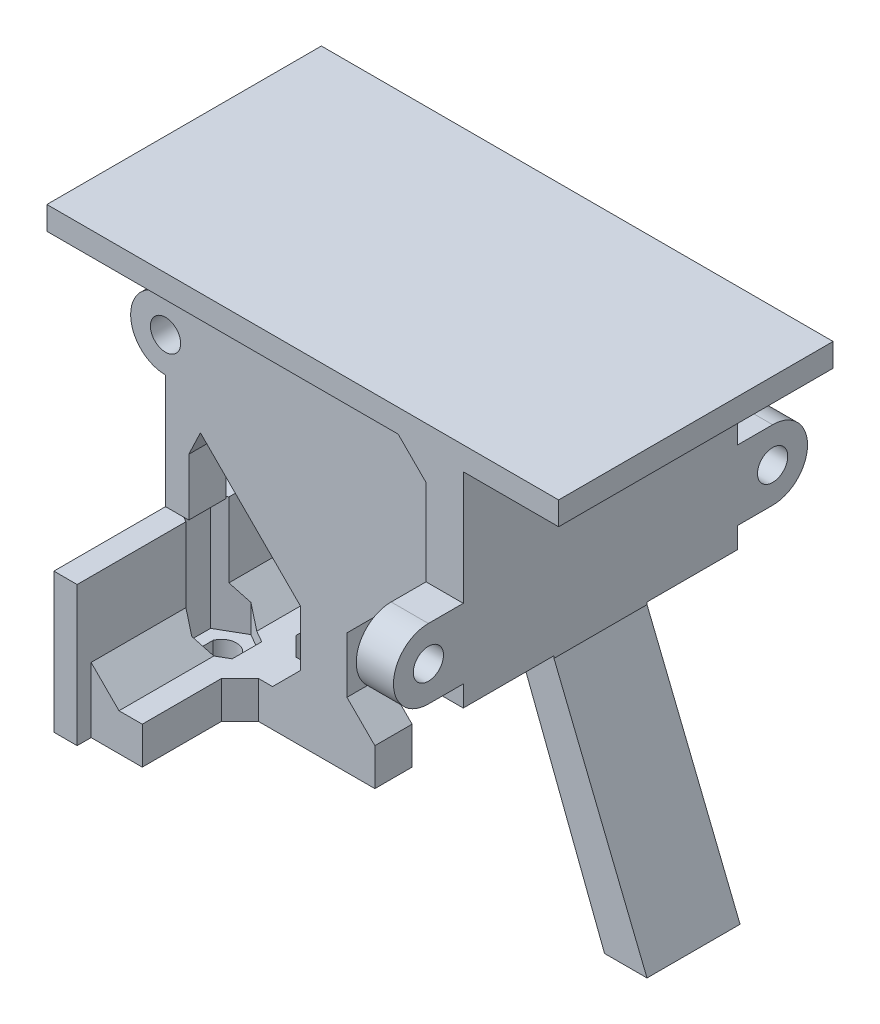
SolidWorks part; units mm, degrees
ref_plane "Alzado" through (0, 0, 0) normal (0, 0, 1) x (1, 0, 0)
ref_plane "Planta" through (0, 0, 0) normal (0, 1, 0) x (1, 0, 0)
ref_plane "Vista lateral" through (0, 0, 0) normal (1, 0, 0) x (0, 0, -1)
sketch "Croquis1" plane through (0, 0, 0) normal (0, 0, 1) x (1, 0, 0)
  line L0 (-14.75, 6) -> (-14.75, 3.75)
  line L1 (-14.75, 6) -> (14.75, 6)
  line L3 (-14.75, -6) -> (14.75, -6)
  line L5 (-14.75, 4.0227) -> (22, -6) construction
  line L6 (-22, -6) -> (22, 6) construction
  line L7 (-14.75, 3.75) -> (-18.5, 3.75)
  line L8 (-18.5, -3.75) -> (-14.75, -3.75)
  line L9 (-14.75, -3.75) -> (-14.75, -6)
  line L10 (14.75, -6) -> (14.75, -3.75)
  line L11 (14.75, -3.75) -> (18.5, -3.75)
  line L12 (14.75, 6) -> (14.75, 3.75)
  line L13 (14.75, 3.75) -> (18.5, 3.75)
  circle A0 centre (-18.5, 0) radius 1.625
  circle A1 centre (18.5, 0) radius 1.625
  arc A2 (-18.5, 3.75) -> (-18.5, -3.75) centre (-18.5, 0) ccw
  arc A3 (18.5, -3.75) -> (18.5, 3.75) centre (18.5, 0) ccw
  point P0 (0, 0)
  dimension "D1" = 3.25
  dimension "D6" = 7.5
  dimension "D7" = 7.5
  dimension "D2" = 37
  dimension "D3" = 18.5
  dimension "D5" = 12
extrude "Saliente-Extruir1" add sketch "Croquis1" along normal blind 4
sketch "Croquis2" plane through (0, 0, 4) normal (0, 0, 1) x (1, 0, 0)
  line L0 (-14.75, -6) -> (14.75, -6) construction
  line L1 (-4, -6) -> (1, -6)
  line L2 (-4, -6) -> (-4, -31)
  line L3 (-4, -31) -> (1, -31)
  line L4 (1, -6) -> (1, -31)
  dimension "D1" = 5
  dimension "D2" = 4
  dimension "D3" = 25
extrude "Saliente-Extruir2" add sketch "Croquis2" against normal blind 4
sketch "Croquis3" plane through (0, -31, 0) normal (0, -1, 0) x (1, 0, 0)
  line L0 (-10.5, -1.5) -> (-10.5, -10.5)
  line L5 (-18.5, 14.5) -> (-10.5, 14.5)
  line L6 (-18.5, 14.5) -> (-18.5, -10.5)
  line L7 (-22.25, 2) -> (-12.4182, 2) construction
  line L13 (-18.5, -10.5) -> (-10.5, -10.5)
  line L15 (-10.5, 14.5) -> (-10.5, 5.5)
  line L16 (-10.5, 5.5) -> (4, 5.5)
  line L19 (-10.5, -1.5) -> (4, -1.5)
  line L20 (4, 5.5) -> (4, -1.5)
  line L21 (-18.5, 4) -> (-18.5, 0) construction
  circle A4 centre (-14.5, 2) radius 1.625
  dimension "D3" = 25
  dimension "D9" = 7
  dimension "D5" = 3.25
  dimension "D10" = 4
  dimension "D1" = 8
  dimension "D2" = 12.5
  dimension "D8" = 3.5
  dimension "D6" = 12.5
extrude "Saliente-Extruir3" add sketch "Croquis3" against normal blind 4
chamfer "Chaflán1" distance 3 angle 45 1 edges at (-4, -27, 2)
chamfer "Chaflán2" distance 1.5 angle 45 2 edges at (-10.5, -29, -1.5) (-10.5, -29, 5.5)
sketch "Croquis4" plane through (0, 0, 4) normal (0, 0, 1) x (1, 0, 0)
  line L1 (18.5, -6) -> (26.25, -6)
  line L2 (18.5, -6) -> (18.5, 6)
  line L3 (18.5, 6) -> (26.25, 6)
  line L4 (26.25, -6) -> (26.25, 6)
  arc A0 (18.5, -3.75) -> (18.5, 3.75) centre (18.5, 0) ccw construction
  circle A1 centre (18.5, 0) radius 1.625 construction
  point P7 (22.25, 0)
  dimension "D1" = 4
  dimension "D2" = 0
extrude "Saliente-Extruir4" add sketch "Croquis4" along normal blind 21 and the other way blind 25
sketch "Croquis5" plane through (0, 6, 0) normal (0, 1, 0) x (1, 0, 0)
  line L0 (26.25, 21) -> (18.5, 21) construction
  line L1 (18.5, 0) -> (22.25, 0)
  line L2 (18.5, 0) -> (18.5, 21)
  line L3 (18.5, 21) -> (22.25, 21)
  line L4 (22.25, 0) -> (22.25, 21)
  line L6 (18.5, -4) -> (22.25, -4)
  line L7 (18.5, -4) -> (18.5, -25)
  line L8 (18.5, -25) -> (22.25, -25)
  line L9 (22.25, -4) -> (22.25, -25)
  line L10 (26.25, -25) -> (18.5, -25) construction
  line L11 (26.25, 21) -> (26.25, -25) construction
  line L12 (14.75, -4) -> (-14.75, -4) construction
  dimension "D1" = 4
  dimension "D2" = 4
extrude "Cortar-Extruir1" cut sketch "Croquis5" against normal through all both and the other way through all
sketch "Croquis6" plane through (0, 0, 4) normal (0, 0, 1) x (1, 0, 0)
  line L0 (18.5, -1.625) -> (18.5, 1.625) construction
  line L1 (18.5, 3.75) -> (22.25, 6)
  line L2 (22.25, 6) -> (18.5, 6)
  line L3 (18.5, 6) -> (18.5, 3.75)
  line L4 (18.5, -3.75) -> (22.25, -6)
  line L5 (22.25, -6) -> (18.5, -6)
  line L6 (18.5, -6) -> (18.5, -3.75)
  circle A0 centre (18.5, 0) radius 1.625
extrude "Cortar-Extruir2" cut sketch "Croquis6" against normal through all both and the other way through all
chamfer "Chaflán4" distance 5 angle 45 2 edges at (22.25, 0, 0) (22.25, 0, 4)
sketch "Croquis7" plane through (0, 0, 4) normal (0, 0, 1) x (1, 0, 0)
  circle A0 centre (18.5, 0) radius 3.745
  dimension "D1" = 7.49
extrude "Cortar-Extruir5" cut sketch "Croquis7" along normal blind 22
sketch "Croquis8" plane through (0, 0, 0) normal (0, 0, -1) x (-1, 0, 0)
  circle A0 centre (-18.5, 0) radius 3.745
extrude "Cortar-Extruir6" cut sketch "Croquis8" along normal blind 22
sketch "Croquis9" plane through (26.25, 0, 0) normal (1, 0, 0) x (0, 0, -1)
  line L1 (-16.75, 6) -> (-16.75, 3.75)
  line L2 (21, 6) -> (-25, 6) construction
  line L3 (-16.75, 3.75) -> (-20.5, 3.75)
  line L4 (-16.75, -6) -> (-16.75, -3.75)
  line L5 (21, -6) -> (-25, -6) construction
  line L6 (-16.75, -3.75) -> (-20.5, -3.75)
  line L7 (12.75, -6) -> (12.75, -3.75)
  line L8 (12.75, -3.75) -> (16.5, -3.75)
  line L9 (12.75, 6) -> (12.75, 3.75)
  line L10 (12.75, 3.75) -> (16.5, 3.75)
  line L11 (-16.75, 6) -> (-25, 6)
  line L12 (-25, 6) -> (-25, -6)
  line L13 (-25, -6) -> (-16.75, -6)
  line L14 (12.75, 6) -> (21, 6)
  line L15 (21, -6) -> (21, 6) construction
  line L16 (21, 6) -> (21, -6)
  line L17 (21, -6) -> (12.75, -6)
  line L18 (-2, 1.625) -> (-2, 19.0588) construction
  line L19 (0, 1.625) -> (-4, 1.625) construction
  arc A2 (-20.5, 3.75) -> (-20.5, -3.75) centre (-20.5, 0) ccw
  arc A3 (16.5, -3.75) -> (16.5, 3.75) centre (16.5, 0) ccw
  dimension "D1" = 37
  dimension "D2" = 18.5
  dimension "D4" = 7.5
extrude "Cortar-Extruir7" cut sketch "Croquis9" against normal blind 22
sketch "Croquis10" plane through (26.25, 0, 0) normal (1, 0, 0) x (0, 0, -1)
  line L0 (-2, -1.625) -> (-2, 16.9497) construction
  circle A0 centre (-20.5, 0) radius 1.625
  circle A1 centre (16.5, 0) radius 1.625
  arc A2 (-20.5, 3.75) -> (-20.5, -3.75) centre (-20.5, 0) ccw construction
  arc A3 (16.5, -3.75) -> (16.5, 3.75) centre (16.5, 0) ccw construction
  dimension "D1" = 3.25
  dimension "D2" = 3.25
extrude "Cortar-Extruir8" cut sketch "Croquis10" against normal blind 22
chamfer "Chaflán5" distance 12 angle 45 2 edges at (-4, -6, 2) (1, -6, 2)
sketch "Croquis11" plane through (0, -31, 0) normal (0, -1, 0) x (1, 0, 0)
  line L0 (4, 2) -> (-9.3695, 2) construction
  line L1 (-18.5, 16) -> (-16, 16)
  line L2 (-18.5, 16) -> (-18.5, -12)
  line L3 (-18.5, -12) -> (-16, -12)
  line L4 (-16, 16) -> (-16, -12)
  line L5 (-18.5, 14.5) -> (-18.5, -10.5) construction
  dimension "D1" = 28
  dimension "D2" = 14
  dimension "D3" = 2.5
extrude "Saliente-Extruir5" add sketch "Croquis11" against normal blind 15
chamfer "Chaflán6" distance 3 angle 45 2 edges at (-16, -27, -4.5625) (-16, -27, 8.5625)
sketch "Croquis12" plane through (0, -31, 0) normal (0, -1, 0) x (1, 0, 0)
  line L13 (-11.75, 0.4123) -> (-11.75, 3.5877)
  line L14 (-11.75, 3.5877) -> (-14.5, 5.1754)
  line L15 (-14.5, 5.1754) -> (-17.25, 3.5877)
  line L16 (-17.25, 3.5877) -> (-17.25, 0.4123)
  line L17 (-17.25, 0.4123) -> (-14.5, -1.1754)
  line L18 (-14.5, -1.1754) -> (-11.75, 0.4123)
  circle A0 centre (-14.5, 2) radius 2.75 construction
  dimension "D1" = 5.5
extrude "Cortar-Extruir9" cut sketch "Croquis12" against normal up to surface (12.5 mm away) from offset 2.5 up to face at (-17.25, -16, 2) offset against normal yes
sketch "Croquis13" plane through (0, -27, 0) normal (0, 1, 0) x (1, 0, 0)
  line L0 (-10.5, 3) -> (-10.5, 2)
  line L1 (-10.5, 2) -> (-8.5, 0)
  line L2 (14.75, 0) -> (-14.75, 0) construction
  line L3 (-8.5, 0) -> (4, 0)
  line L4 (4, 0) -> (4, 5.165)
  line L5 (4, 5.165) -> (-10.5, 3)
  line L6 (-18.5, -2) -> (0.9317, -2) construction
  line L7 (-18.5, -4) -> (-18.5, 0) construction
  line L8 (4, -9.165) -> (-10.5, -7)
  line L9 (4, -4) -> (4, -9.165)
  line L10 (-8.5, -4) -> (4, -4)
  line L11 (-10.5, -6) -> (-8.5, -4)
  line L12 (-10.5, -7) -> (-10.5, -6)
  dimension "D1" = 2
  dimension "D2" = 2
extrude "Cortar-Extruir10" cut sketch "Croquis13" against normal blind 10
sketch "Croquis14" plane through (26.25, 0, 0) normal (1, 0, 0) x (0, 0, -1)
  line L0 (2, -31) -> (10.5, -31) construction
  line L1 (-7, -6) -> (3, -6)
  line L2 (-7, -6) -> (-7, -31)
  line L3 (-7, -31) -> (3, -31)
  line L4 (3, -6) -> (3, -31)
  line L5 (-4, -27) -> (-4, -18) construction
  dimension "D1" = 10
  dimension "D2" = 3
  dimension "D3" = 25
extrude "Saliente-Extruir6" add sketch "Croquis14" against normal blind 8 and the other way blind 10
sketch "Croquis15" plane through (0, 6, 0) normal (0, 1, 0) x (1, 0, 0)
  line L0 (14.75, -4) -> (14.75, 0) construction
  line L1 (-14.75, -4) -> (14.75, -4)
  line L2 (-14.75, -4) -> (-14.75, 0)
  line L3 (-14.75, 0) -> (14.75, 0)
  line L4 (14.75, -4) -> (14.75, 0)
  line L6 (22.25, 12.75) -> (26.25, 12.75)
  line L7 (22.25, 12.75) -> (22.25, -16.75)
  line L8 (22.25, -16.75) -> (26.25, -16.75)
  line L9 (26.25, 12.75) -> (26.25, -16.75)
extrude "Saliente-Extruir7" add sketch "Croquis15" along normal blind 10
sketch "Croquis16" plane through (0, 16, 0) normal (0, 1, 0) x (1, 0, 0)
  line L1 (-18.5, 12.75) -> (36.5, 12.75)
  line L2 (-18.5, 12.75) -> (-18.5, -16.75)
  line L3 (-18.5, -16.75) -> (36.5, -16.75)
  line L4 (36.5, 12.75) -> (36.5, -16.75)
  line L6 (26.25, 12.75) -> (22.25, 12.75) construction
  line L7 (-18.5, -16) -> (-18.5, 12) construction
  dimension "D1" = 29.5
  dimension "D2" = 55
extrude "Saliente-Extruir8" add sketch "Croquis16" along normal blind 2.5
chamfer "Chaflán7" distance 3 angle 45 3 edges at (14.75, 16, 2) (-14.75, 16, 2) (22.25, 16, 2)
sketch "Croquis17" plane through (0, 0, 4) normal (0, 0, 1) x (1, 0, 0)
  line L0 (-18.5, -16) -> (-18.5, -3.75)
  line L1 (-18.5, -3.75) -> (-14.75, -3.75)
  line L2 (-14.75, -3.75) -> (-14.75, -7.25)
  line L3 (-14.75, -7.25) -> (-16, -9.875)
  line L4 (-16, -9.875) -> (-16, -16)
  line L5 (-16, -16) -> (-18.5, -16)
extrude "Saliente-Extruir9" add sketch "Croquis17" against normal up to surface (4 mm away) up to face at (0.9325, -7.3558, 0)
chamfer "Chaflán11" distance 3 3 edges at (2.5, -27, 0) (2.5, -27, 4) (1, -27, 2)
chamfer "Chaflán12" distance 25 angle 22 1 edges at (36.25, -6, 2) first distance on face at (36.25, -18.5, 2)
chamfer "Chaflán14" distance 35 angle 21 1 edges at (18.25, -31, 2) first distance on face at (18.25, -18.5, 2)
